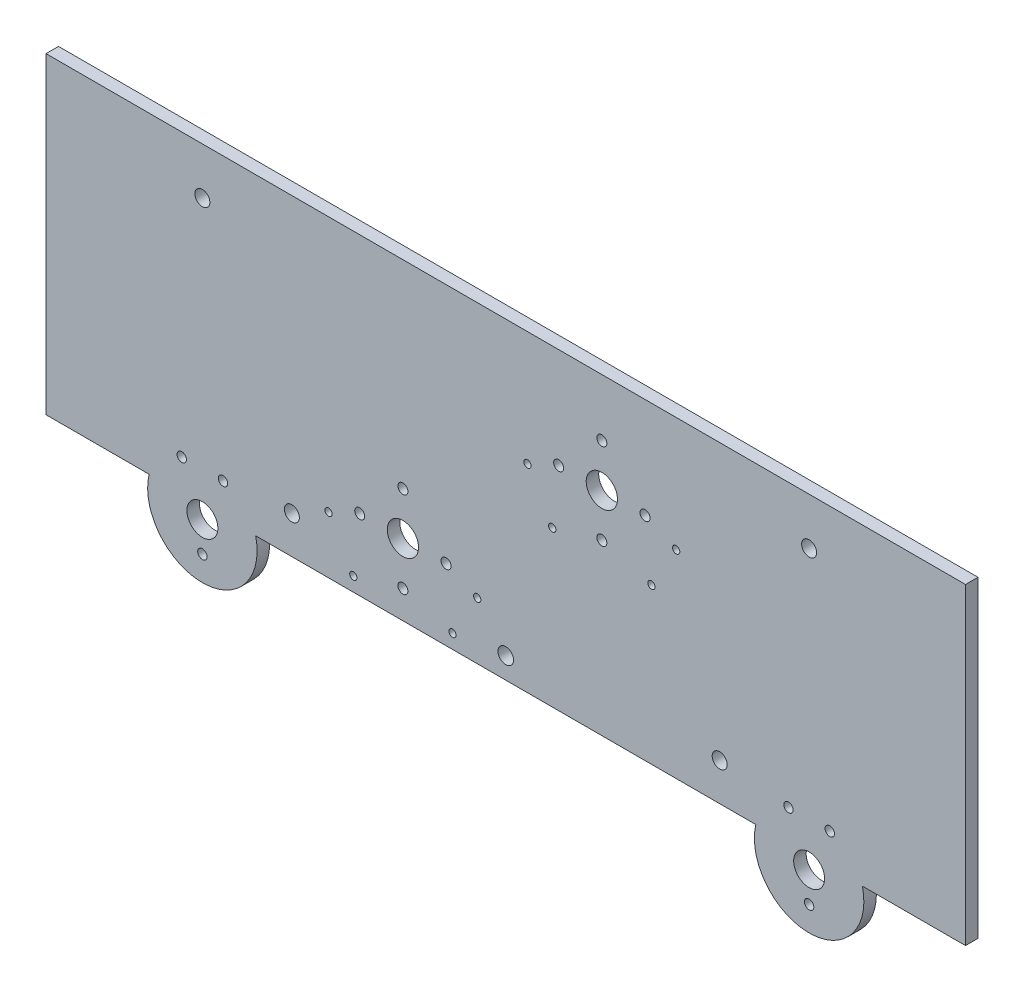
SolidWorks part; units mm, degrees
ref_plane "Front Plane" through (0, 0, 0) normal (0, 0, 1) x (1, 0, 0)
ref_plane "Top Plane" through (0, 0, 0) normal (0, 1, 0) x (1, 0, 0)
ref_plane "Right Plane" through (0, 0, 0) normal (1, 0, 0) x (0, 0, -1)
sketch "Sketch2" plane through (0, 0, 0) normal (0, 0, 1) x (1, 0, 0)
  line L0 (-123.19, -36.83) -> (-123.19, -31.75) construction
  line L1 (-186.69, -31.75) -> (186.69, -31.75)
  line L2 (-186.69, -31.75) -> (-186.69, 31.75)
  line L3 (-186.69, 31.75) -> (186.69, 31.75)
  line L4 (186.69, -31.75) -> (186.69, 31.75)
  line L5 (-186.69, -31.75) -> (186.69, 31.75) construction
  line L6 (-186.69, 31.75) -> (186.69, -31.75) construction
  line L7 (0, 0) -> (0, -31.75) construction
  line L8 (123.19, -36.83) -> (123.19, -31.75) construction
  line L16 (-186.69, 31.75) -> (186.69, 31.75)
  line L17 (-186.69, 31.75) -> (-186.69, 95.25)
  line L18 (-186.69, 95.25) -> (186.69, 95.25)
  line L19 (186.69, 31.75) -> (186.69, 95.25)
  circle A0 centre (-123.19, -36.83) radius 6.2865
  circle A1 centre (123.19, -36.83) radius 6.2865
  circle A2 centre (-123.19, -36.83) radius 22.225
  circle A3 centre (123.19, -36.83) radius 22.225
  circle A4 centre (-123.19, 76.2) radius 3.048
  circle A5 centre (123.19, 76.2) radius 3.048
  circle A7 centre (86.868, -16.51) radius 3.048
  circle A8 centre (-86.868, -16.51) radius 3.048
  point P0 (0, 0)
  point P27 (-86.868, -16.51)
  dimension "D3" = 123.19
  dimension "D5" = 5.08
  dimension "D7" = 63.5
  dimension "D8" = 44.45
  dimension "D4" = 12.573
  dimension "D9" = 12.573
  dimension "D10" = 44.45
  dimension "D13" = 6.096
  dimension "D14" = 6.096
  dimension "D19" = 6.096
  dimension "D20" = 6.096
  dimension "D1" = 63.5
  dimension "D2" = 373.38
  dimension "D6" = 123.19
  dimension "D11" = 107.95
  dimension "D12" = 107.95
  dimension "D15" = 86.868
  dimension "D16" = 15.24
  dimension "D17" = 15.24
  dimension "D18" = 86.868
extrude "Boss-Extrude1" add sketch "Sketch2" against normal blind 5.0749 contours A1 L1 L4 L3 L2 A0 | L3 L19 L18 L17 | A2 | A3 region at (0, 1.2473, 0) region at (0, 63.4687, 0)
extrude "Cut-Extrude11" cut sketch "Sketch2<4>" against normal through all contours L1 A0 | L1 A1 | A0 | A1 region at (-123.19, -37.1167, 0) region at (123.19, -37.1167, 0)
sketch "Sketch2<4>" plane through (0, 0, 0) normal (0, 0, 1) x (1, 0, 0) same geometry as "Sketch2"
ref_plane "Plane1" through (-186.69, 95.25, 0) normal (0, 1, 0) x (1, 0, 0)
ref_plane "Plane2" through (0, 0, -5.0749) normal (0, 0, -1) x (-1, 0, 0)
sketch "Sketch3" plane through (0, 0, 0) normal (0, 0, 1) x (1, 0, 0)
  circle A0 centre (-41.7701, -2.8148) radius 22.86
  circle A1 centre (39.02, 54.5075) radius 22.86
  circle A2 centre (-41.7701, -2.8148) radius 6.35
  circle A3 centre (39.02, 54.5075) radius 6.35
  circle A4 centre (-59.2961, -2.8148) radius 2.032
  circle A5 centre (-41.7701, 14.7112) radius 2.032
  circle A6 centre (-41.7701, -20.3408) radius 2.032
  circle A7 centre (-24.2441, -2.8148) radius 2.032
  circle A8 centre (21.494, 54.5075) radius 2.032
  circle A9 centre (56.546, 54.5075) radius 2.032
  circle A10 centre (39.02, 72.0335) radius 2.032
  circle A11 centre (39.02, 36.9815) radius 2.032
  point P0 (-41.7701, -2.8148)
  point P1 (39.02, 54.5075)
  point P2 (-45.441, 4.8991)
  point P3 (39.3668, 54.8259)
  point P4 (39.3668, 54.8259)
  point P29 (39.3668, 54.8259)
  point P30 (-45.2574, 4.5553)
  point P31 (-40.6517, -5.6267)
  point P32 (-41.7701, -2.8148)
  dimension "D5" = 45.72
  dimension "D6" = 12.7
  dimension "D7" = 12.7
  dimension "D12" = 4.064
  dimension "D15" = 4.064
  dimension "D2" = 88.2396
  dimension "D3" = 124.206
  dimension "D4" = 99.06
  dimension "D8" = 17.526
  dimension "D9" = 17.526
  dimension "D10" = 17.526
  dimension "D11" = 17.526
  dimension "D13" = 17.526
  dimension "D14" = 17.526
  dimension "D16" = 17.526
  dimension "D17" = 17.526
extrude "Cut-Extrude12" cut sketch "Sketch3" against normal through all contours A2 | A7 | A3 | A9 | A10 | A8 | A5 | A4 | A6 | A11 region at (-41.7701, -2.8148, 0) region at (39.02, 54.5075, 0) region at (-24.2441, -2.8148, 0) region at (21.494, 54.5075, 0) region at (56.546, 54.5075, 0) region at (39.02, 72.0335, 0)
sketch "Sketch5" plane through (0, 0, 0) normal (0, 0, 1) x (1, 0, 0)
  line L0 (-41.7701, -2.8148) -> (-41.7701, -33.5488) construction
  line L1 (39.02, 54.5075) -> (39.02, 23.7735) construction
  line L2 (-71.9539, -8.6043) -> (-11.5864, -8.6043) construction
  line L3 (-61.9073, -26.0328) -> (-21.633, -26.0328) construction
  line L4 (18.8828, 31.2895) -> (59.1571, 31.2895) construction
  line L5 (8.8362, 48.718) -> (69.2037, 48.718) construction
  circle A0 centre (-41.7701, -2.8148) radius 30.734
  circle A1 centre (39.02, 54.5075) radius 30.734
  circle A2 centre (-61.9073, -26.0328) radius 1.4732
  circle A3 centre (-21.633, -26.0328) radius 1.4732
  circle A4 centre (-71.9539, -8.6043) radius 1.4732
  circle A5 centre (-11.5864, -8.6043) radius 1.4732
  circle A6 centre (18.8828, 31.2895) radius 1.4732
  circle A7 centre (59.1571, 31.2895) radius 1.4732
  circle A8 centre (8.8362, 48.718) radius 1.4732
  circle A9 centre (69.2037, 48.718) radius 1.4732
  circle A10 centre (-41.7701, -33.5488) radius 1.4732
  circle A11 centre (39.02, 23.7735) radius 1.4732
  point P25 (0, 0)
  dimension "D1" = 61.468
  dimension "D2" = 61.468
  dimension "D5" = 2.9464
  dimension "D8" = 2.9464
  dimension "D3" = 21.4941
  dimension "D4" = 20.1168
  dimension "D6" = 21.4941
  dimension "D7" = 20.1168
extrude "Cut-Extrude13" cut sketch "Sketch5" against normal through all contours A1 A8 | A1 A8 | A1 A9 | A1 A9 | A1 A7 | A4 | A2 | A3 | A5 | A6 | A7 region at (9.4564, 48.837, 0) region at (8.2284, 48.6014, 0) region at (69.8115, 48.6014, 0) region at (68.5835, 48.837, 0) region at (58.7433, 31.7666, 0)
sketch "Sketch7" plane through (0, 0, 0) normal (0, 0, 1) x (1, 0, 0)
  line L0 (-123.19, -36.83) -> (-123.19, -59.055) construction
  line L1 (-131.572, -19.05) -> (-114.808, -19.05) construction
  line L2 (123.19, -36.83) -> (123.19, -59.055) construction
  line L3 (114.808, -19.05) -> (131.572, -19.05)
  circle A0 centre (-123.19, -36.83) radius 22.225 construction
  circle A1 centre (-123.19, -49.022) radius 1.905
  circle A2 centre (-131.572, -19.05) radius 1.905
  circle A3 centre (-114.808, -19.05) radius 1.905
  circle A4 centre (123.19, -36.83) radius 22.225 construction
  circle A5 centre (123.19, -49.022) radius 1.905
  circle A6 centre (114.808, -19.05) radius 1.905
  circle A7 centre (131.572, -19.05) radius 1.905
  point P15 (-123.19, -19.05)
  point P23 (123.19, -19.05)
  dimension "D4" = 3.81
  dimension "D6" = 3.81
  dimension "D1" = 12.192
  dimension "D2" = 17.78
  dimension "D3" = 16.764
  dimension "D5" = 12.192
  dimension "D7" = 17.78
  dimension "D8" = 16.764
extrude "Cut-Extrude14" cut sketch "Sketch7" against normal through all contours A2 | A1 | A6 | A7 | A5 | A3 region at (131.572, -17.1989, 0) region at (112.9569, -19.05, 0) region at (-123.19, -49.022, 0) region at (-131.572, -19.05, 0) region at (123.19, -49.022, 0)
sketch "Sketch8" plane through (0, 0, 0) normal (0, 0, 1) x (1, 0, 0)
  line L0 (0, 0) -> (0, -31.75) construction
  circle A0 centre (0, -23.114) radius 3.175
  dimension "D2" = 6.35
  dimension "D1" = 8.636
extrude "Cut-Extrude15" cut sketch "Sketch8" against normal through all contours A0
